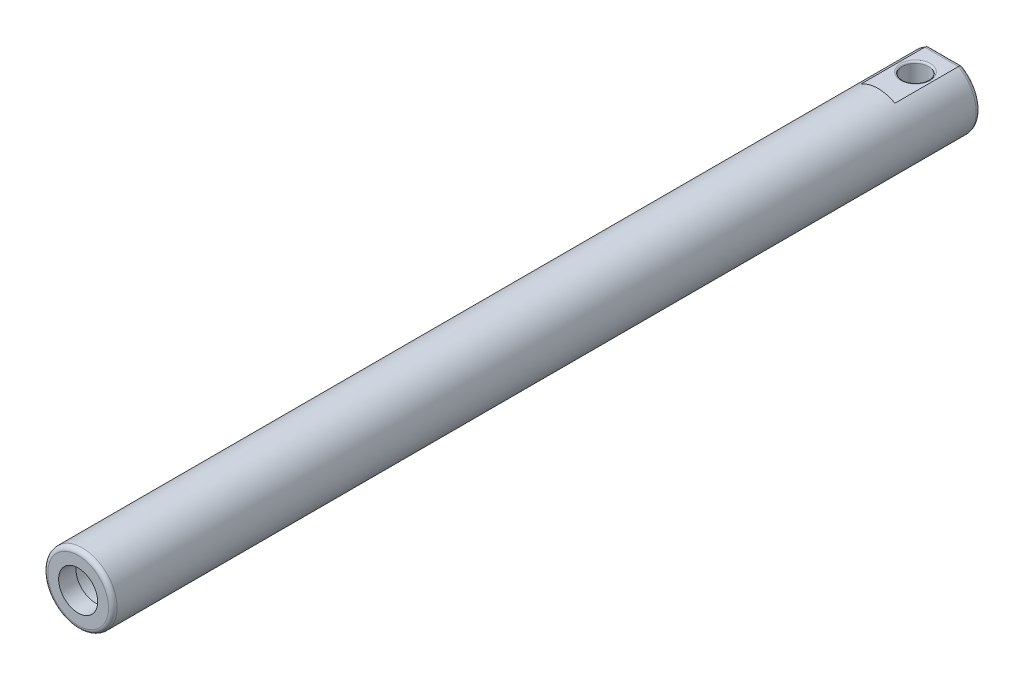
SolidWorks part; units mm, degrees
material "Alloy Steel"
ref_plane "Front" through (0, 0, 0) normal (0, 0, 1) x (1, 0, 0)
ref_plane "Top" through (0, 0, 0) normal (0, 1, 0) x (1, 0, 0)
ref_plane "Right" through (0, 0, 0) normal (1, 0, 0) x (0, 0, -1)
sketch "Sketch2" plane through (0, 0, 0) normal (0, 0, 1) x (1, 0, 0)
  circle A0 centre (0, 0) radius 40
  dimension "D1" = 80
extrude "Boss-Extrude1" add sketch "Sketch2" along normal blind 920
sketch "Sketch3" plane through (0, 0, 0) normal (0, 0, -1) x (-1, 0, 0)
  circle A0 centre (0, 0) radius 30
  dimension "60" = 60
extrude "Cut-Extrude1" cut sketch "Sketch3" against normal blind 900
sketch "Sketch4" plane through (0, 0, 920) normal (0, 0, 1) x (1, 0, 0)
  circle A0 centre (0, 0) radius 22.5
  dimension "D1" = 45
extrude "Cut-Extrude2" cut sketch "Sketch4" against normal up to next
sketch "Sketch5" plane through (0, 0, 0) normal (0, 0, -1) x (-1, 0, 0)
  circle A0 centre (0, 0) radius 40 construction
  circle A1 centre (0, 0) radius 40
extrude "Boss-Extrude2" add sketch "Sketch5" along normal blind 80
ref_plane "Plane1" through (0, 40, 0) normal (0, 1, 0) x (1, 0, 0)
sketch "Sketch6" plane through (0, 40, 0) normal (0, 1, 0) x (1, 0, 0)
  line L1 (20, 80) -> (-20, 80)
  line L2 (20, 80) -> (20, 2)
  line L3 (20, 2) -> (-20, 2)
  line L4 (-20, 80) -> (-20, 2)
  line L5 (20, 80) -> (-20, 2) construction
  line L6 (20, 2) -> (-20, 80) construction
  line L7 (40, 80) -> (-40, 80) construction
  point P0 (0, 41)
  dimension "D1" = 78
  dimension "D2" = 40
extrude "Cut-Extrude3" cut sketch "Sketch6" against normal blind 5
mirror "Mirror1" about plane through (0, 0, 0) normal (0, 1, 0) of "Cut-Extrude3"
sketch "Sketch7" plane through (0, 35, 0) normal (0, 1, 0) x (1, 0, 0)
  line L1 (19.3649, 80) -> (-19.3649, 80) construction
  circle A0 centre (0, 45) radius 15
  dimension "D1" = 30
  dimension "D2" = 35
extrude "Cut-Extrude4" cut sketch "Sketch7" against normal through all
fillet "Fillet2" radius 5 5 edges at (0, -35, -80) (0, 35, -80) (40, 0, -80) (-40, 0, -80) (40, 0, 920)
fillet "Fillet3" radius 2 2 edges at (0, -35, -30) (0, 35, -30)
